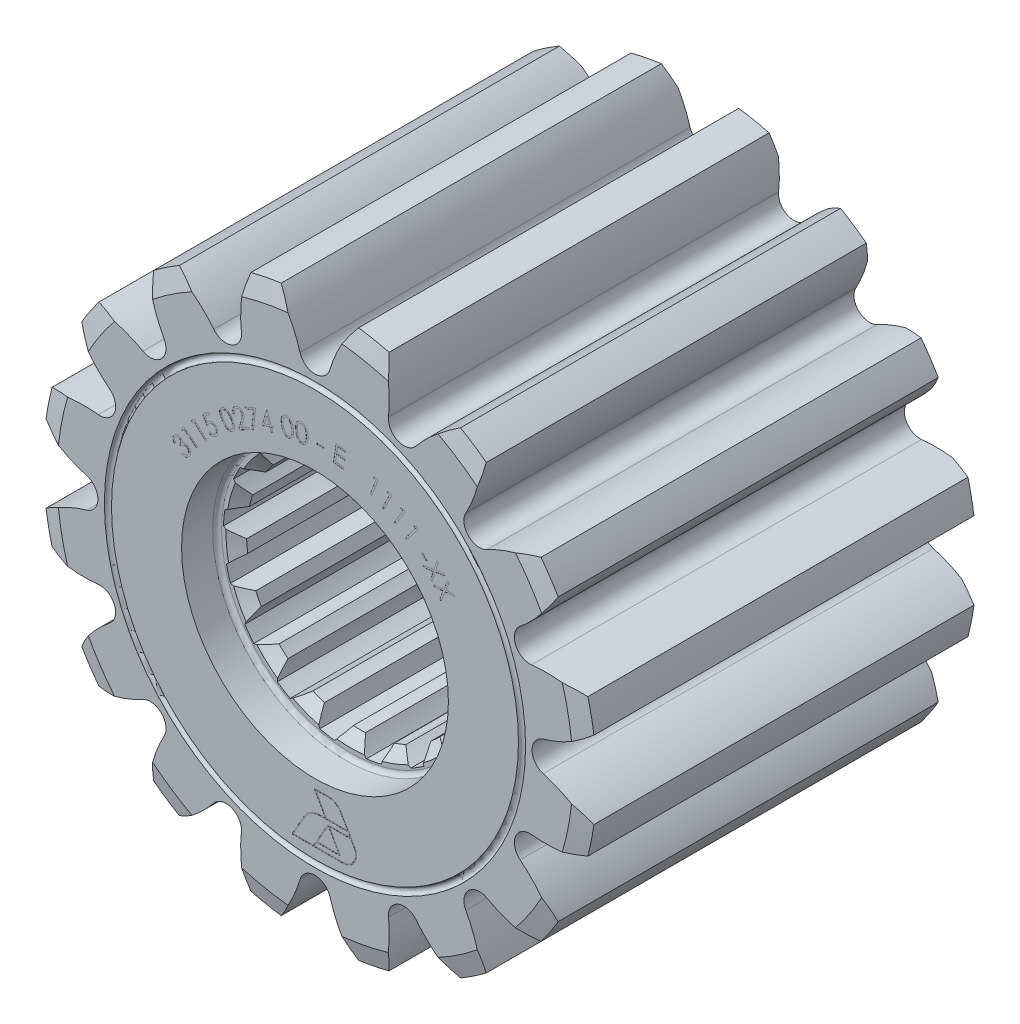
SolidWorks part; units mm, degrees
material "EN39B"
ref_plane "Front Plane" through (0, 0, 0) normal (0, 0, 1) x (1, 0, 0)
ref_plane "Top Plane" through (0, 0, 0) normal (0, 1, 0) x (1, 0, 0)
ref_plane "Right Plane" through (0, 0, 0) normal (1, 0, 0) x (0, 0, -1)
sketch "Sketch2" plane through (0, 0, 0) normal (1, 0, 0) x (0, 0, -1)
  line L0 (0, 15) -> (0, 22.875)
  line L1 (-4, 14.5) -> (-4, 14)
  line L2 (0, 23.675) -> (0, 29)
  line L3 (0, 29) -> (-0.5627, 31.1)
  line L4 (-0.5627, 31.1) -> (-43.2873, 31.1)
  line L5 (0, 15) -> (-3.5, 15)
  line L6 (-39.85, 14) -> (-38.85, 12.69)
  line L7 (-5, 12.69) -> (-38.85, 12.69)
  line L8 (-43.85, 29) -> (-43.2873, 31.1)
  line L9 (-21.925, 53.6422) -> (-21.925, 0) construction
  line L10 (0, 0) -> (-49.8392, 0) construction
  line L11 (-43.85, 23.675) -> (-43.85, 29)
  line L12 (-4, 14) -> (-5, 12.69)
  line L13 (-43.85, 15) -> (-43.85, 22.875)
  line L14 (-43.85, 15) -> (-40.35, 15)
  line L15 (-39.85, 14.5) -> (-39.85, 14)
  arc A0 (0, 23.675) -> (0, 22.875) centre (0, 23.275) ccw
  arc A1 (-43.85, 23.675) -> (-43.85, 22.875) centre (-43.85, 23.275) cw
  arc A2 (-3.5, 15) -> (-4, 14.5) centre (-3.5, 14.5) ccw
  arc A3 (-40.35, 15) -> (-39.85, 14.5) centre (-40.35, 14.5) cw
  point P17 (-21.925, 31.1)
  point P25 (-21.925, 12.69)
  point P28 (-3.9867, 15)
  point P29 (-39.8633, 15)
  dimension "D11" = 28
  dimension "D12" = 0.5
  dimension "D2" = 46.55
  dimension "D5" = 0.4
  dimension "D3" = 4
  dimension "D4" = 30
  dimension "D6" = 62.2
  dimension "D7" = 58
  dimension "D8" = 15
  dimension "D9" = 25.38
  dimension "D10" = 5
  dimension "D13" = 43.85
revolve "Revolve1" add sketch "Sketch2" angle 360 about L10
sketch "Sketch3" plane through (0, 0, 0) normal (0, 0, 1) x (1, 0, 0)
  line L0 (0, 0) -> (0, 38.1308) construction
  arc A0 (4.35, 30.7943) -> (-4.35, 30.7943) centre (0, 0) ccw
  circle A1 centre (0, 0) radius 31.1 construction
  arc A2 (-1.6791, 25.6605) -> (1.6791, 25.6605) centre (0, 26.1535) ccw
  arc A3 (-1.6791, 25.6605) -> (-4.35, 30.7943) centre (-16.0715, 21.4344) ccw
  arc A4 (1.6791, 25.6605) -> (4.35, 30.7943) centre (16.0715, 21.4344) cw
  dimension "D1" = 3.5
  dimension "D3" = 24.4035
  dimension "D4" = 15
  dimension "D2" = 8.7
extrude "Cut-Extrude1" cut sketch "Sketch3" along normal through all
ref_axis "Axis1" through (0, 0, 5) along (0, 0, 1)
pattern_circular "CirPattern1" count 16 over 360 about axis through (0, 0, 5) along (0, 0, 1) of "Cut-Extrude1"
sketch "Sketch4" plane through (0, 0, 0) normal (0, 0, 1) x (1, 0, 0)
  line L0 (0, 0) -> (0, 18.0332) construction
  arc A0 (0.85, 14.2647) -> (-0.85, 14.2647) centre (0, 0) ccw
  arc A1 (1.65, 12.5823) -> (-1.65, 12.5823) centre (0, 0) ccw
  arc A2 (-0.85, 14.2647) -> (-1.65, 12.5823) centre (12.0667, 7.0913) ccw
  circle A3 centre (0, 0) radius 12.69 construction
  arc A4 (0.85, 14.2647) -> (1.65, 12.5823) centre (-12.0667, 7.0913) cw
  dimension "D1" = 28.58
  dimension "D4" = 14.7749
  dimension "D2" = 1.7
  dimension "D3" = 3.3
extrude "Cut-Extrude2" cut sketch "Sketch4" along normal through all
pattern_circular "CirPattern2" count 17 over 360 about axis through (0, 0, 5) along (0, 0, 1) of "Cut-Extrude2"
sketch "Sketch5" plane through (0, 0, 43.85) normal (0, 0, 1) x (1, 0, 0)
  arc A0 (-16.9034, 1.8097) -> (16.8186, 2.4766) centre (0, 0) cw construction
  text T0 "3115 0274 00 - E   1111 -XX" font "Century Gothic" height 2
  line B0 (3.1801, -21.6612) -> (-0.0884, -21.6612)
  line B1 (2.6959, -20.995) -> (0.2905, -20.995)
  line B2 (-0.0315, -21.5612) -> (0.2336, -21.095)
  line B3 (1.1696, -18.217) -> (0.5996, -18.217)
  line B4 (-0.0884, -15.9531) -> (1.1696, -18.217)
  line B5 (2.6959, -20.995) -> (1.5115, -18.8477)
  line B6 (4.1409, -18.8477) -> (4.4397, -19.3641)
  line B7 (1.5157, -15.9531) -> (-0.0884, -15.9531)
  line B8 (3.7969, -18.217) -> (4.1409, -18.8477)
  line B9 (3.7969, -18.217) -> (2.9331, -16.7604)
  line B10 (-0.0884, -21.6612) -> (-2.5858, -21.6612)
  line B11 (-1.1817, -19.1921) -> (-2.5858, -21.6612)
  line B12 (3.9952, -18.7474) -> (3.74, -18.317)
  line B13 (1.5157, -16.0531) -> (0.0816, -16.0531)
  line B14 (0.0816, -16.0531) -> (1.284, -18.217)
  line B15 (0.5996, -18.317) -> (3.74, -18.317)
  line B16 (-1.0961, -19.2438) -> (-2.4139, -21.5612)
  line B17 (-0.1465, -21.5612) -> (-2.4139, -21.5612)
  line B18 (1.4535, -18.7474) -> (3.9952, -18.7474)
  line B19 (-0.1465, -21.5612) -> (1.4535, -18.7474)
  line B20 (4.0254, -18.8477) -> (4.3542, -19.4161)
  line B21 (3.1801, -21.5612) -> (-0.0315, -21.5612)
  line B22 (1.284, -18.217) -> (3.6807, -18.217)
  line B23 (3.6807, -18.217) -> (2.8471, -16.8115)
  line B24 (2.8653, -21.095) -> (0.2336, -21.095)
  line B25 (2.8653, -21.095) -> (1.6257, -18.8477)
  line B26 (1.6257, -18.8477) -> (4.0254, -18.8477)
  line B27 (0.2905, -20.995) -> (1.5115, -18.8477)
  arc B28 (2.9331, -16.7604) -> (1.5157, -15.9531) centre (1.5157, -17.6011) ccw
  arc B29 (3.1801, -21.6612) -> (4.4397, -19.3641) centre (3.1801, -20.1673) ccw
  arc B30 (0.5996, -18.217) -> (-1.1817, -19.1921) centre (0.5996, -20.3317) ccw
  arc B31 (2.8471, -16.8115) -> (1.5157, -16.0531) centre (1.5157, -17.6011) ccw
  arc B32 (0.5996, -18.317) -> (-1.0961, -19.2438) centre (0.5996, -20.3317) ccw
  arc B33 (3.1801, -21.5612) -> (4.3542, -19.4161) centre (3.1801, -20.1673) ccw
  dimension "D1" = 17
sketch_block_instance "SKETCH LOGO-1"
sketch_block "SKETCH LOGO" parameters "D1"=29.059, "D2"=11.4163, "D3"=29.624, "D4"=6.8884
extrude "PARTNO" cut sketch "Sketch5" against normal blind 0.01
